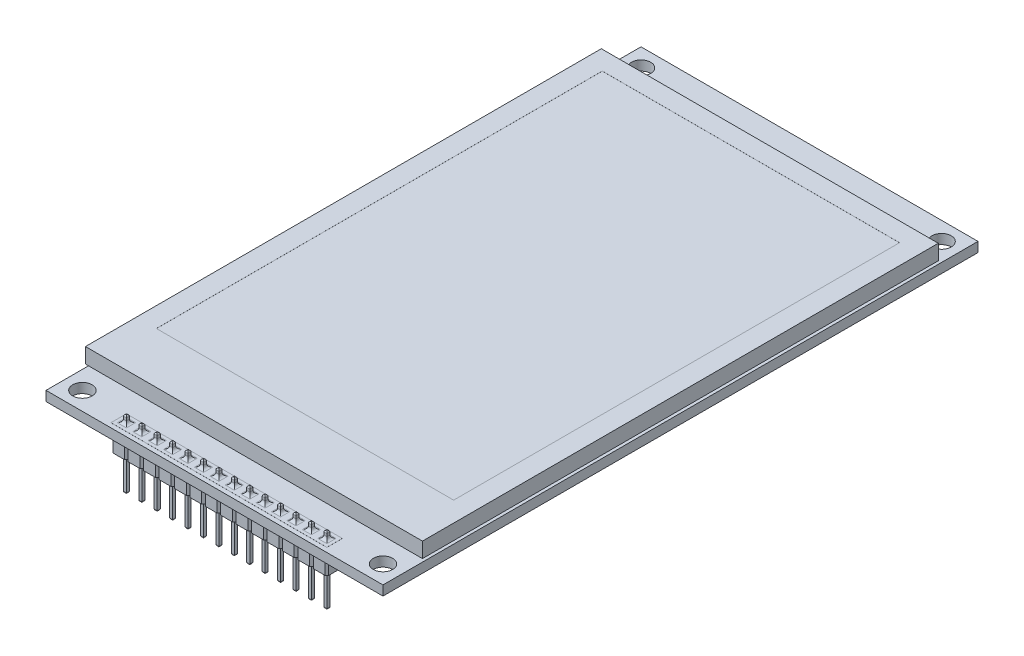
SolidWorks part; units mm, degrees
ref_plane "前视基准面" through (0, 0, 0) normal (0, 0, 1) x (1, 0, 0)
ref_plane "上视基准面" through (0, 0, 0) normal (0, 1, 0) x (1, 0, 0)
ref_plane "右视基准面" through (0, 0, 0) normal (1, 0, 0) x (0, 0, -1)
other "Configuration Table"
sketch "草图1" plane through (0, 0, 0) normal (0, 1, 0) x (1, 0, 0)
  line L0 (27.75, 0) -> (27.75, -98) construction
  line L1 (0, 0) -> (55.5, 0)
  line L2 (0, 0) -> (0, -98)
  line L3 (0, -98) -> (55.5, -98)
  line L4 (55.5, 0) -> (55.5, -98)
  line L5 (0, -96) -> (55.5, -96) construction
  line L7 (9.97, -94.73) -> (45.53, -94.73)
  line L8 (9.97, -94.73) -> (9.97, -97.27)
  line L9 (9.97, -97.27) -> (45.53, -97.27)
  line L10 (45.53, -94.73) -> (45.53, -97.27)
  circle A0 centre (3, -3) radius 1.6
  circle A1 centre (52.5, -3) radius 1.6
  circle A2 centre (3, -95) radius 1.6
  circle A3 centre (52.5, -95) radius 1.6
  dimension "D3" = 3.2
  dimension "D4" = 3.2
  dimension "D5" = 3.2
  dimension "D6" = 3.2
  dimension "D7" = 24.75
  dimension "D9" = 24.75
  dimension "D10" = 24.75
  dimension "D11" = 3
  dimension "D12" = 3
  dimension "D13" = 92
  dimension "D14" = 92
  dimension "D1" = 55.5
  dimension "D2" = 98
  dimension "D8" = 24.75
  dimension "D15" = 2
  dimension "D16" = 1.27
  dimension "D17" = 1.27
  dimension "D18" = 17.78
  dimension "D19" = 17.78
extrude "凸台-拉伸1" add sketch "草图1" along normal blind 1.6
sketch "草图2" plane through (0, 1.6, 0) normal (0, 1, 0) x (1, 0, 0)
  line L1 (9.97, -94.73) -> (45.53, -94.73)
  line L2 (9.97, -94.73) -> (9.97, -97.27)
  line L3 (9.97, -97.27) -> (45.53, -97.27)
  line L4 (45.53, -94.73) -> (45.53, -97.27)
extrude "凸台-拉伸2" add sketch "草图2" against normal blind 1.62 from offset 0.01
sketch "草图3" plane through (0, 1.61, 0) normal (0, 1, 0) x (1, 0, 0)
  line L0 (9.97, -96) -> (45.53, -96) construction
  line L1 (9.97, -94.73) -> (9.97, -97.27) construction
  line L2 (45.53, -97.27) -> (45.53, -94.73) construction
  line L3 (13.53, -96.25) -> (14.03, -96.25)
  line L4 (10.99, -95.75) -> (11.49, -95.75)
  line L5 (10.99, -95.75) -> (10.99, -96.25)
  line L6 (10.99, -96.25) -> (11.49, -96.25)
  line L7 (11.49, -95.75) -> (11.49, -96.25)
  line L8 (10.99, -95.75) -> (11.49, -96.25) construction
  line L9 (10.99, -96.25) -> (11.49, -95.75) construction
  line L10 (14.03, -95.75) -> (14.03, -96.25)
  line L11 (13.53, -95.75) -> (14.03, -95.75)
  line L12 (13.53, -95.75) -> (13.53, -96.25)
  line L13 (16.07, -96.25) -> (16.57, -96.25)
  line L14 (16.57, -95.75) -> (16.57, -96.25)
  line L15 (16.07, -95.75) -> (16.57, -95.75)
  line L16 (16.07, -95.75) -> (16.07, -96.25)
  line L17 (18.61, -96.25) -> (19.11, -96.25)
  line L18 (19.11, -95.75) -> (19.11, -96.25)
  line L19 (18.61, -95.75) -> (19.11, -95.75)
  line L20 (18.61, -95.75) -> (18.61, -96.25)
  line L21 (21.15, -96.25) -> (21.65, -96.25)
  line L22 (21.65, -95.75) -> (21.65, -96.25)
  line L23 (21.15, -95.75) -> (21.65, -95.75)
  line L24 (21.15, -95.75) -> (21.15, -96.25)
  line L25 (23.69, -96.25) -> (24.19, -96.25)
  line L26 (24.19, -95.75) -> (24.19, -96.25)
  line L27 (23.69, -95.75) -> (24.19, -95.75)
  line L28 (23.69, -95.75) -> (23.69, -96.25)
  line L29 (26.23, -96.25) -> (26.73, -96.25)
  line L30 (26.73, -95.75) -> (26.73, -96.25)
  line L31 (26.23, -95.75) -> (26.73, -95.75)
  line L32 (26.23, -95.75) -> (26.23, -96.25)
  line L33 (28.77, -96.25) -> (29.27, -96.25)
  line L34 (29.27, -95.75) -> (29.27, -96.25)
  line L35 (28.77, -95.75) -> (29.27, -95.75)
  line L36 (28.77, -95.75) -> (28.77, -96.25)
  line L37 (31.31, -96.25) -> (31.81, -96.25)
  line L38 (31.81, -95.75) -> (31.81, -96.25)
  line L39 (31.31, -95.75) -> (31.81, -95.75)
  line L40 (31.31, -95.75) -> (31.31, -96.25)
  line L41 (33.85, -96.25) -> (34.35, -96.25)
  line L42 (34.35, -95.75) -> (34.35, -96.25)
  line L43 (33.85, -95.75) -> (34.35, -95.75)
  line L44 (33.85, -95.75) -> (33.85, -96.25)
  line L45 (36.39, -96.25) -> (36.89, -96.25)
  line L46 (36.89, -95.75) -> (36.89, -96.25)
  line L47 (36.39, -95.75) -> (36.89, -95.75)
  line L48 (36.39, -95.75) -> (36.39, -96.25)
  line L49 (38.93, -96.25) -> (39.43, -96.25)
  line L50 (39.43, -95.75) -> (39.43, -96.25)
  line L51 (38.93, -95.75) -> (39.43, -95.75)
  line L52 (38.93, -95.75) -> (38.93, -96.25)
  line L53 (41.47, -96.25) -> (41.97, -96.25)
  line L54 (41.97, -95.75) -> (41.97, -96.25)
  line L55 (41.47, -95.75) -> (41.97, -95.75)
  line L56 (41.47, -95.75) -> (41.47, -96.25)
  line L57 (44.01, -96.25) -> (44.51, -96.25)
  line L58 (44.51, -95.75) -> (44.51, -96.25)
  line L59 (44.01, -95.75) -> (44.51, -95.75)
  line L60 (44.01, -95.75) -> (44.01, -96.25)
  point P6 (11.24, -96)
  point P11 (11.24, -95.75)
  dimension "D1" = 0.5
  dimension "D2" = 0.5
  dimension "D3" = 1.27
  dimension "D4" = 14
extrude "凸台-拉伸3" add sketch "草图3" along normal blind 1.18 and the other way blind 9.99
sketch "草图4" plane through (0, -0.01, 0) normal (0, -1, 0) x (1, 0, 0)
  line L0 (45.53, 94.73) -> (9.97, 94.73) construction
  line L1 (9.97, 97.27) -> (12.51, 97.27)
  line L2 (9.97, 97.27) -> (9.97, 94.73)
  line L3 (9.97, 94.73) -> (12.51, 94.73)
  line L4 (12.51, 97.27) -> (12.51, 94.73)
  line L5 (15.05, 97.27) -> (17.59, 97.27)
  line L6 (17.59, 97.27) -> (17.59, 94.73)
  line L7 (15.05, 94.73) -> (17.59, 94.73)
  line L8 (15.05, 97.27) -> (15.05, 94.73)
  line L9 (20.13, 97.27) -> (22.67, 97.27)
  line L10 (22.67, 97.27) -> (22.67, 94.73)
  line L11 (20.13, 94.73) -> (22.67, 94.73)
  line L12 (20.13, 97.27) -> (20.13, 94.73)
  line L13 (25.21, 97.27) -> (27.75, 97.27)
  line L14 (27.75, 97.27) -> (27.75, 94.73)
  line L15 (25.21, 94.73) -> (27.75, 94.73)
  line L16 (25.21, 97.27) -> (25.21, 94.73)
  line L17 (30.29, 97.27) -> (32.83, 97.27)
  line L18 (32.83, 97.27) -> (32.83, 94.73)
  line L19 (30.29, 94.73) -> (32.83, 94.73)
  line L20 (30.29, 97.27) -> (30.29, 94.73)
  line L21 (35.37, 97.27) -> (37.91, 97.27)
  line L22 (37.91, 97.27) -> (37.91, 94.73)
  line L23 (35.37, 94.73) -> (37.91, 94.73)
  line L24 (35.37, 97.27) -> (35.37, 94.73)
  line L25 (40.45, 97.27) -> (42.99, 97.27)
  line L26 (42.99, 97.27) -> (42.99, 94.73)
  line L27 (40.45, 94.73) -> (42.99, 94.73)
  line L28 (40.45, 97.27) -> (40.45, 94.73)
  dimension "D1" = 2.54
  dimension "D2" = 7
extrude "凸台-拉伸4" add sketch "草图4" along normal blind 2.54
chamfer "倒角1" distance 0.3 angle 45 28 edges at (12.51, -1.28, 94.73) (12.51, -1.28, 97.27) (15.05, -1.28, 97.27) (15.05, -1.28, 94.73) (17.59, -1.28, 94.73) (17.59, -1.28, 97.27) (20.13, -1.28, 97.27) (20.13, -1.28, 94.73) (22.67, -1.28, 94.73) (22.67, -1.28, 97.27) (25.21, -1.28, 97.27) (25.21, -1.28, 94.73) (27.75, -1.28, 94.73) (27.75, -1.28, 97.27) (9.97, -1.275, 94.73) (30.29, -1.28, 97.27) (30.29, -1.28, 94.73) (32.83, -1.28, 94.73) (32.83, -1.28, 97.27) (9.97, -1.275, 97.27) (35.37, -1.28, 97.27) (35.37, -1.28, 94.73) (37.91, -1.28, 94.73) (37.91, -1.28, 97.27) (40.45, -1.28, 97.27) (40.45, -1.28, 94.73) (42.99, -1.28, 94.73) (42.99, -1.28, 97.27)
sketch "草图5" plane through (0, -0.01, 0) normal (0, -1, 0) x (1, 0, 0)
  line L1 (12.51, 96.97) -> (12.81, 97.27)
  line L2 (10.27, 97.27) -> (45.53, 97.27) construction
  line L3 (12.81, 97.27) -> (14.75, 97.27)
  line L5 (15.05, 96.97) -> (14.75, 97.27)
  line L7 (15.35, 94.73) -> (12.21, 94.73) construction
  line L8 (14.75, 94.73) -> (15.05, 95.03)
  line L9 (15.05, 95.03) -> (15.05, 96.97)
  line L10 (12.51, 96.97) -> (12.51, 95.03)
  line L11 (12.51, 95.03) -> (12.81, 94.73)
  line L12 (12.81, 94.73) -> (14.75, 94.73)
  line L13 (17.59, 96.97) -> (17.89, 97.27)
  line L14 (17.89, 97.27) -> (19.83, 97.27)
  line L15 (20.13, 96.97) -> (19.83, 97.27)
  line L16 (19.83, 94.73) -> (20.13, 95.03)
  line L17 (20.13, 95.03) -> (20.13, 96.97)
  line L18 (17.59, 96.97) -> (17.59, 95.03)
  line L19 (17.59, 95.03) -> (17.89, 94.73)
  line L20 (17.89, 94.73) -> (19.83, 94.73)
  line L21 (22.67, 96.97) -> (22.97, 97.27)
  line L22 (22.97, 97.27) -> (24.91, 97.27)
  line L23 (25.21, 96.97) -> (24.91, 97.27)
  line L24 (24.91, 94.73) -> (25.21, 95.03)
  line L25 (25.21, 95.03) -> (25.21, 96.97)
  line L26 (22.67, 96.97) -> (22.67, 95.03)
  line L27 (22.67, 95.03) -> (22.97, 94.73)
  line L28 (22.97, 94.73) -> (24.91, 94.73)
  line L29 (27.75, 96.97) -> (28.05, 97.27)
  line L30 (28.05, 97.27) -> (29.99, 97.27)
  line L31 (30.29, 96.97) -> (29.99, 97.27)
  line L32 (29.99, 94.73) -> (30.29, 95.03)
  line L33 (30.29, 95.03) -> (30.29, 96.97)
  line L34 (27.75, 96.97) -> (27.75, 95.03)
  line L35 (27.75, 95.03) -> (28.05, 94.73)
  line L36 (28.05, 94.73) -> (29.99, 94.73)
  line L37 (32.83, 96.97) -> (33.13, 97.27)
  line L38 (33.13, 97.27) -> (35.07, 97.27)
  line L39 (35.37, 96.97) -> (35.07, 97.27)
  line L40 (35.07, 94.73) -> (35.37, 95.03)
  line L41 (35.37, 95.03) -> (35.37, 96.97)
  line L42 (32.83, 96.97) -> (32.83, 95.03)
  line L43 (32.83, 95.03) -> (33.13, 94.73)
  line L44 (33.13, 94.73) -> (35.07, 94.73)
  line L45 (37.91, 96.97) -> (38.21, 97.27)
  line L46 (38.21, 97.27) -> (40.15, 97.27)
  line L47 (40.45, 96.97) -> (40.15, 97.27)
  line L48 (40.15, 94.73) -> (40.45, 95.03)
  line L49 (40.45, 95.03) -> (40.45, 96.97)
  line L50 (37.91, 96.97) -> (37.91, 95.03)
  line L51 (37.91, 95.03) -> (38.21, 94.73)
  line L52 (38.21, 94.73) -> (40.15, 94.73)
  line L53 (42.99, 96.97) -> (43.29, 97.27)
  line L54 (43.29, 97.27) -> (45.23, 97.27)
  line L55 (45.53, 96.97) -> (45.23, 97.27)
  line L56 (45.23, 94.73) -> (45.53, 95.03)
  line L57 (45.53, 95.03) -> (45.53, 96.97)
  line L58 (42.99, 96.97) -> (42.99, 95.03)
  line L59 (42.99, 95.03) -> (43.29, 94.73)
  line L60 (43.29, 94.73) -> (45.23, 94.73)
  dimension "D1" = 7
extrude "凸台-拉伸5" add sketch "草图5" along normal blind 2.54
fillet "圆角1" radius 0.5 56 edges at (11.24, 1.61, 95.75) (10.99, 1.61, 96) (11.24, 1.61, 96.25) (11.49, 1.61, 96) (44.26, 1.61, 95.75) (44.01, 1.61, 96) (44.26, 1.61, 96.25) (44.51, 1.61, 96) (41.72, 1.61, 95.75) (41.47, 1.61, 96) (41.72, 1.61, 96.25) (41.97, 1.61, 96) (39.18, 1.61, 95.75) (38.93, 1.61, 96) (39.18, 1.61, 96.25) (39.43, 1.61, 96) (36.64, 1.61, 95.75) (36.39, 1.61, 96) (36.64, 1.61, 96.25) (36.89, 1.61, 96) (34.1, 1.61, 95.75) (33.85, 1.61, 96) (34.1, 1.61, 96.25) (34.35, 1.61, 96) (31.56, 1.61, 95.75) (31.31, 1.61, 96) (31.56, 1.61, 96.25) (31.81, 1.61, 96) (29.02, 1.61, 95.75) (28.77, 1.61, 96) (29.02, 1.61, 96.25) (29.27, 1.61, 96) (26.48, 1.61, 95.75) (26.23, 1.61, 96) (26.48, 1.61, 96.25) (26.73, 1.61, 96) (23.94, 1.61, 95.75) (23.69, 1.61, 96) (23.94, 1.61, 96.25) (24.19, 1.61, 96) (21.4, 1.61, 95.75) (21.15, 1.61, 96) (21.4, 1.61, 96.25) (21.65, 1.61, 96) (18.86, 1.61, 95.75) (18.61, 1.61, 96) (18.86, 1.61, 96.25) (19.11, 1.61, 96) (16.32, 1.61, 95.75) (16.07, 1.61, 96) (16.32, 1.61, 96.25) (16.57, 1.61, 96) (13.78, 1.61, 95.75) (13.53, 1.61, 96) (13.78, 1.61, 96.25) (14.03, 1.61, 96)
fillet "圆角2" radius 0.25 112 edges at (44.26, -8.38, 95.75) (44.01, -8.38, 96) (44.26, -8.38, 96.25) (44.51, -8.38, 96) (41.72, -8.38, 95.75) (41.47, -8.38, 96) (41.72, -8.38, 96.25) (41.97, -8.38, 96) (39.18, -8.38, 95.75) (38.93, -8.38, 96) (39.18, -8.38, 96.25) (39.43, -8.38, 96) (36.64, -8.38, 95.75) (36.39, -8.38, 96) (36.64, -8.38, 96.25) (36.89, -8.38, 96) (34.1, -8.38, 95.75) (33.85, -8.38, 96) (34.1, -8.38, 96.25) (34.35, -8.38, 96) (31.56, -8.38, 95.75) (31.31, -8.38, 96) (31.56, -8.38, 96.25) (31.81, -8.38, 96) (29.02, -8.38, 95.75) (28.77, -8.38, 96) (29.02, -8.38, 96.25) (29.27, -8.38, 96) (26.48, -8.38, 95.75) (26.23, -8.38, 96) (26.48, -8.38, 96.25) (26.73, -8.38, 96) (23.94, -8.38, 95.75) (23.69, -8.38, 96) (23.94, -8.38, 96.25) (24.19, -8.38, 96) (21.4, -8.38, 95.75) (21.15, -8.38, 96) (21.4, -8.38, 96.25) (21.65, -8.38, 96) (18.86, -8.38, 95.75) (18.61, -8.38, 96) (18.86, -8.38, 96.25) (19.11, -8.38, 96) (16.32, -8.38, 95.75) (16.07, -8.38, 96) (16.32, -8.38, 96.25) (16.57, -8.38, 96) (13.78, -8.38, 95.75) (13.53, -8.38, 96) (13.78, -8.38, 96.25) (14.03, -8.38, 96) (11.24, -8.38, 95.75) (10.99, -8.38, 96) (11.24, -8.38, 96.25) (11.49, -8.38, 96) (44.26, 2.79, 96.25) (44.01, 2.79, 96) (44.26, 2.79, 95.75) (44.51, 2.79, 96) (41.72, 2.79, 96.25) (41.47, 2.79, 96) (41.72, 2.79, 95.75) (41.97, 2.79, 96) (39.18, 2.79, 96.25) (38.93, 2.79, 96) (39.18, 2.79, 95.75) (39.43, 2.79, 96) (36.64, 2.79, 96.25) (36.39, 2.79, 96) (36.64, 2.79, 95.75) (36.89, 2.79, 96) (34.1, 2.79, 96.25) (33.85, 2.79, 96) (34.1, 2.79, 95.75) (34.35, 2.79, 96) (31.56, 2.79, 96.25) (31.31, 2.79, 96) (31.56, 2.79, 95.75) (31.81, 2.79, 96) (29.02, 2.79, 96.25) (28.77, 2.79, 96) (29.02, 2.79, 95.75) (29.27, 2.79, 96) (26.48, 2.79, 96.25) (26.23, 2.79, 96) (26.48, 2.79, 95.75) (26.73, 2.79, 96) (23.94, 2.79, 96.25) (23.69, 2.79, 96) (23.94, 2.79, 95.75) (24.19, 2.79, 96) (21.4, 2.79, 96.25) (21.15, 2.79, 96) (21.4, 2.79, 95.75) (21.65, 2.79, 96) (18.86, 2.79, 96.25) (18.61, 2.79, 96) (18.86, 2.79, 95.75) (19.11, 2.79, 96) (16.32, 2.79, 96.25) (16.07, 2.79, 96) (16.32, 2.79, 95.75) (16.57, 2.79, 96) (13.78, 2.79, 96.25) (13.53, 2.79, 96) (13.78, 2.79, 95.75) (14.03, 2.79, 96) (11.24, 2.79, 96.25) (10.99, 2.79, 96) (11.24, 2.79, 95.75) (11.49, 2.79, 96)
sketch "草图6" plane through (0, 1.6, 0) normal (0, 1, 0) x (1, 0, 0)
  line L0 (0, 0) -> (0, -98) construction
  line L1 (0, -6.54) -> (55.5, -6.54)
  line L2 (0, -6.54) -> (0, -91.5)
  line L3 (0, -91.5) -> (55.5, -91.5)
  line L4 (55.5, -6.54) -> (55.5, -91.5)
  line L5 (55.5, -98) -> (55.5, 0) construction
  line L6 (55.5, 0) -> (0, 0) construction
  line L8 (3.27, -9.65) -> (52.23, -9.65)
  line L9 (3.27, -9.65) -> (3.27, -83.09)
  line L10 (3.27, -83.09) -> (52.23, -83.09)
  line L11 (52.23, -9.65) -> (52.23, -83.09)
  point P14 (27.75, 0)
  dimension "D1" = 84.96
  dimension "D2" = 6.54
  dimension "D3" = 48.96
  dimension "D4" = 24.48
  dimension "D5" = 73.44
  dimension "D6" = 9.65
extrude "凸台-拉伸6" add sketch "草图6" along normal blind 2.5 from offset 0.5 separate body
sketch "草图7" plane through (0, 1.6, 0) normal (0, 1, 0) x (1, 0, 0)
  line L1 (3.27, -9.65) -> (52.23, -9.65)
  line L2 (3.27, -9.65) -> (3.27, -83.09)
  line L3 (3.27, -83.09) -> (52.23, -83.09)
  line L4 (52.23, -9.65) -> (52.23, -83.09)
extrude "凸台-拉伸7" add sketch "草图7" along normal blind 2.99
sketch "草图8" plane through (0, 0, 0) normal (0, -1, 0) x (1, 0, 0)
  line L0 (0, 0) -> (0, 98) construction
  line L1 (14.9446, 82.4535) -> (46.5814, 82.4535)
  line L2 (14.9446, 82.4535) -> (14.9446, 70.9331)
  line L3 (14.9446, 70.9331) -> (46.5814, 70.9331)
  line L4 (46.5814, 82.4535) -> (46.5814, 70.9331)
  line L5 (0, 51.7029) -> (14.9446, 51.7029)
  line L6 (0, 51.7029) -> (0, 42.3979)
  line L7 (0, 42.3979) -> (14.9446, 42.3979)
  line L8 (14.9446, 51.7029) -> (14.9446, 42.3979)
  line L10 (35.6814, 55.4248) -> (42.4164, 55.4248)
  line L11 (35.6814, 55.4248) -> (35.6814, 49.6646)
  line L12 (35.6814, 49.6646) -> (42.4164, 49.6646)
  line L13 (42.4164, 55.4248) -> (42.4164, 49.6646)
  line L14 (21.3252, 29.9913) -> (28.9464, 29.9913)
  line L15 (21.3252, 29.9913) -> (21.3252, 23.4336)
  line L16 (21.3252, 23.4336) -> (28.9464, 23.4336)
  line L17 (28.9464, 29.9913) -> (28.9464, 23.4336)
  line L18 (37.8082, 28.3962) -> (46.5814, 28.3962)
  line L19 (37.8082, 28.3962) -> (37.8082, 21.2181)
  line L20 (37.8082, 21.2181) -> (46.5814, 21.2181)
  line L21 (46.5814, 28.3962) -> (46.5814, 21.2181)
  line L22 (47.1131, 36.5491) -> (50.8351, 36.5491)
  line L23 (47.1131, 36.5491) -> (47.1131, 32.384)
  line L24 (47.1131, 32.384) -> (50.8351, 32.384)
  line L25 (50.8351, 36.5491) -> (50.8351, 32.384)
  line L26 (30.763, 40.2711) -> (36.6562, 40.2711)
  line L27 (30.763, 40.2711) -> (30.763, 36.5491)
  line L28 (30.763, 36.5491) -> (36.6562, 36.5491)
  line L29 (36.6562, 40.2711) -> (36.6562, 36.5491)
  line L30 (39.0489, 43.2841) -> (43.3912, 43.2841)
  line L31 (39.0489, 43.2841) -> (39.0489, 40.2711)
  line L32 (39.0489, 40.2711) -> (43.3912, 40.2711)
  line L33 (43.3912, 43.2841) -> (43.3912, 40.2711)
  line L34 (30.763, 47.0504) -> (33.7096, 47.0504)
  line L35 (30.763, 47.0504) -> (30.763, 44.0817)
  line L36 (30.763, 44.0817) -> (33.7096, 44.0817)
  line L37 (33.7096, 47.0504) -> (33.7096, 44.0817)
  line L38 (12.7292, 26.7124) -> (15.8308, 26.7124)
  line L39 (12.7292, 26.7124) -> (12.7292, 22.8132)
  line L40 (12.7292, 22.8132) -> (15.8308, 22.8132)
  line L41 (15.8308, 26.7124) -> (15.8308, 22.8132)
  line L42 (21.3252, 18.5595) -> (28.9464, 18.5595)
  line L43 (21.3252, 18.5595) -> (21.3252, 15.2806)
  line L44 (21.3252, 15.2806) -> (28.9464, 15.2806)
  line L45 (28.9464, 18.5595) -> (28.9464, 15.2806)
  line L46 (35.6814, 17.762) -> (39.0489, 17.762)
  line L47 (35.6814, 17.762) -> (35.6814, 15.2806)
  line L48 (35.6814, 15.2806) -> (39.0489, 15.2806)
  line L49 (39.0489, 17.762) -> (39.0489, 15.2806)
  line L50 (46.5814, 17.5213) -> (49.7717, 17.5213)
  line L51 (46.5814, 17.5213) -> (46.5814, 16.5213)
  line L52 (46.5814, 16.5213) -> (49.7717, 16.5213)
  line L53 (49.7717, 17.5213) -> (49.7717, 16.5213)
  dimension "D1" = 1
extrude "凸台-拉伸8" add sketch "草图8" along normal blind 2.2
